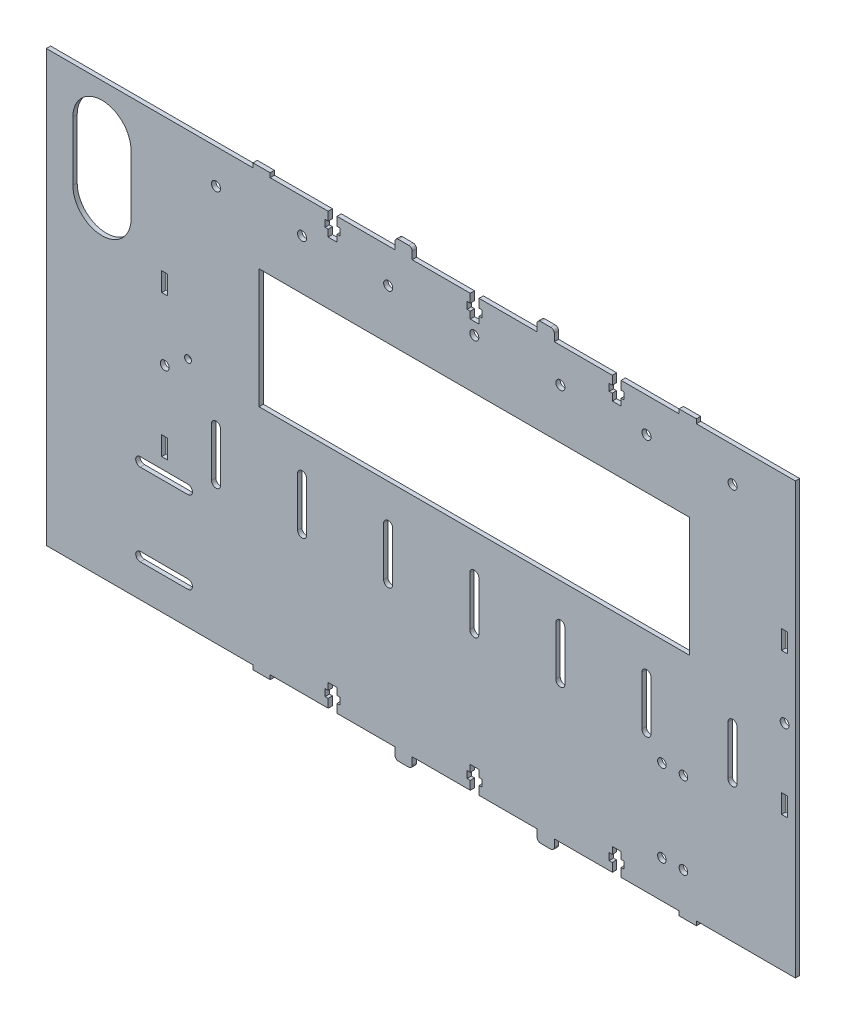
SolidWorks part; units mm, degrees
ref_plane "前视基准面" through (0, 0, 0) normal (0, 0, 1) x (1, 0, 0)
ref_plane "上视基准面" through (0, 0, 0) normal (0, 1, 0) x (1, 0, 0)
ref_plane "右视基准面" through (0, 0, 0) normal (1, 0, 0) x (0, 0, -1)
sketch "草图1" plane through (0, 0, 0) normal (0, 0, 1) x (1, 0, 0)
  line L0 (0, 0) -> (0, -4)
  line L1 (0, -4) -> (-1.45, -4)
  line L2 (-1.45, -4) -> (-1.45, -7.2)
  line L3 (-1.45, -7.2) -> (0, -7.2)
  line L4 (0, -7.2) -> (0, -10.4)
  line L5 (0, -10.4) -> (4.1, -10.4)
  line L6 (4.1, -10.4) -> (4.1, -7.2)
  line L7 (4.1, -7.2) -> (5.55, -7.2)
  line L8 (5.55, -7.2) -> (5.55, -4)
  line L9 (5.55, -4) -> (4.1, -4)
  line L10 (4.1, -4) -> (4.1, 0)
  line L11 (0, 0) -> (-26.95, 0)
  line L12 (-26.95, 0) -> (-26.95, 5)
  line L13 (-26.95, 5) -> (-34.95, 5)
  line L14 (-34.95, 5) -> (-34.95, 0)
  line L15 (2.05, -10.4) -> (2.05, -56.6) construction
  line L16 (-30.95, 5) -> (-30.95, 0) construction
  line L17 (-67.45, -4) -> (-66, -4)
  line L18 (-66, -7.2) -> (-67.45, -7.2)
  line L19 (-60.45, -7.2) -> (-61.9, -7.2)
  line L20 (-61.9, -4) -> (-60.45, -4)
  line L21 (-66, -4) -> (-66, 0)
  line L22 (-66, -10.4) -> (-66, -7.2)
  line L23 (-61.9, -10.4) -> (-66, -10.4)
  line L24 (-61.9, -7.2) -> (-61.9, -10.4)
  line L25 (-67.45, -7.2) -> (-67.45, -4)
  line L26 (-60.45, -4) -> (-60.45, -7.2)
  line L27 (-61.9, 0) -> (-61.9, -4)
  line L28 (-61.9, 0) -> (-34.95, 0)
  line L29 (31.05, 5) -> (39.05, 5)
  line L30 (31.05, 0) -> (31.05, 5)
  line L31 (39.05, 5) -> (39.05, 0)
  line L32 (4.1, 0) -> (31.05, 0)
  line L33 (66, 0) -> (39.05, 0)
  line L34 (66, 0) -> (66, -4)
  line L35 (64.55, -4) -> (64.55, -7.2)
  line L36 (71.55, -7.2) -> (71.55, -4)
  line L37 (66, -7.2) -> (66, -10.4)
  line L38 (66, -10.4) -> (70.1, -10.4)
  line L39 (70.1, -10.4) -> (70.1, -7.2)
  line L40 (70.1, -4) -> (70.1, 0)
  line L41 (66, -4) -> (64.55, -4)
  line L42 (64.55, -7.2) -> (66, -7.2)
  line L43 (70.1, -7.2) -> (71.55, -7.2)
  line L44 (71.55, -4) -> (70.1, -4)
  line L45 (68.05, -10.4) -> (68.05, -6.6) construction
  line L46 (70.1, 0) -> (97.05, 0)
  line L47 (132, 0) -> (105.05, 0)
  line L48 (97.05, 5) -> (97.05, 0)
  line L49 (105.05, 0) -> (105.05, 5)
  line L50 (105.05, 5) -> (97.05, 5)
  line L51 (-63.95, -10.4) -> (-63.95, -6.6) construction
  line L52 (-96.95, 5) -> (-96.95, 0) construction
  line L53 (-66, 0) -> (-92.95, 0)
  line L54 (-92.95, 5) -> (-92.95, 0)
  line L55 (-100.95, 5) -> (-92.95, 5)
  line L56 (-100.95, 0) -> (-100.95, 5)
  line L57 (-127.9, 0) -> (-100.95, 0)
  line L58 (2.05, -10.4) -> (-140.5, -10.4) construction
  line L59 (-127.9, 0) -> (-139.95, 0)
  line L60 (132, 0) -> (144.05, 0)
  line L64 (-139.95, 0) -> (-141.95, 0)
  line L66 (-96.95, -205) -> (-96.95, -200) construction
  line L79 (-63.95, -189.6) -> (-63.95, -193.4) construction
  line L101 (68.05, -189.6) -> (68.05, -193.4) construction
  line L102 (-30.95, -205) -> (-30.95, -200) construction
  line L103 (-127.9, -200) -> (-100.95, -200)
  line L104 (-100.95, -200) -> (-100.95, -205)
  line L137 (-141.95, 0) -> (-141.95, -200) construction
  line L138 (-141.95, -200) -> (-139.95, -200)
  line L140 (-143.35, -62.6) -> (-140.55, -62.6)
  line L141 (-143.35, -62.6) -> (-143.35, -71.4)
  line L142 (-143.35, -71.4) -> (-140.55, -71.4)
  line L143 (-140.55, -62.6) -> (-140.55, -71.4)
  line L144 (-143.35, -62.6) -> (-140.55, -71.4) construction
  line L145 (-143.35, -71.4) -> (-140.55, -62.6) construction
  line L146 (-141.95, -100) -> (-134.9383, -100) construction
  line L148 (-140.55, -137.4) -> (-140.55, -128.6)
  line L149 (-143.35, -137.4) -> (-143.35, -128.6)
  line L150 (-143.35, -128.6) -> (-140.55, -128.6)
  line L151 (-143.35, -137.4) -> (-140.55, -137.4)
  line L152 (-141.95, 0) -> (-146.95, 0)
  line L154 (-146.95, -200) -> (-141.95, -200)
  line L156 (146.05, -200) -> (144.05, -200)
  line L157 (151.05, -200) -> (146.05, -200)
  line L158 (144.05, 0) -> (146.05, 0)
  line L159 (146.05, 0) -> (151.05, 0)
  line L160 (151.05, 0) -> (151.05, -200)
  line L161 (146.05, -100) -> (139.0383, -100) construction
  line L162 (147.45, -71.4) -> (144.65, -62.6) construction
  line L163 (147.45, -62.6) -> (144.65, -71.4) construction
  line L164 (146.05, 0) -> (146.05, -200) construction
  line L165 (147.45, -137.4) -> (144.65, -137.4)
  line L166 (147.45, -128.6) -> (144.65, -128.6)
  line L167 (147.45, -137.4) -> (147.45, -128.6)
  line L168 (144.65, -137.4) -> (144.65, -128.6)
  line L169 (144.65, -62.6) -> (144.65, -71.4)
  line L170 (147.45, -71.4) -> (144.65, -71.4)
  line L171 (147.45, -62.6) -> (147.45, -71.4)
  line L172 (147.45, -62.6) -> (144.65, -62.6)
  line L173 (-100.95, -205) -> (-92.95, -205)
  line L174 (-92.95, -205) -> (-92.95, -200)
  line L175 (-66, -200) -> (-92.95, -200)
  line L176 (105.05, -205) -> (97.05, -205)
  line L177 (105.05, -200) -> (105.05, -205)
  line L178 (97.05, -205) -> (97.05, -200)
  line L179 (132, -200) -> (105.05, -200)
  line L180 (70.1, -200) -> (97.05, -200)
  line L181 (71.55, -196) -> (70.1, -196)
  line L182 (70.1, -192.8) -> (71.55, -192.8)
  line L183 (64.55, -192.8) -> (66, -192.8)
  line L184 (66, -196) -> (64.55, -196)
  line L185 (70.1, -196) -> (70.1, -200)
  line L186 (70.1, -189.6) -> (70.1, -192.8)
  line L187 (66, -189.6) -> (70.1, -189.6)
  line L188 (66, -192.8) -> (66, -189.6)
  line L189 (71.55, -192.8) -> (71.55, -196)
  line L190 (64.55, -196) -> (64.55, -192.8)
  line L191 (66, -200) -> (66, -196)
  line L192 (66, -200) -> (39.05, -200)
  line L193 (4.1, -200) -> (31.05, -200)
  line L194 (39.05, -205) -> (39.05, -200)
  line L195 (31.05, -200) -> (31.05, -205)
  line L196 (31.05, -205) -> (39.05, -205)
  line L197 (-61.9, -200) -> (-34.95, -200)
  line L198 (-61.9, -200) -> (-61.9, -196)
  line L199 (-60.45, -196) -> (-60.45, -192.8)
  line L200 (-67.45, -192.8) -> (-67.45, -196)
  line L201 (-61.9, -192.8) -> (-61.9, -189.6)
  line L202 (-61.9, -189.6) -> (-66, -189.6)
  line L203 (-66, -189.6) -> (-66, -192.8)
  line L204 (-66, -196) -> (-66, -200)
  line L205 (-61.9, -196) -> (-60.45, -196)
  line L206 (-60.45, -192.8) -> (-61.9, -192.8)
  line L207 (-66, -192.8) -> (-67.45, -192.8)
  line L208 (-67.45, -196) -> (-66, -196)
  line L209 (-34.95, -205) -> (-34.95, -200)
  line L210 (-26.95, -205) -> (-34.95, -205)
  line L211 (-26.95, -200) -> (-26.95, -205)
  line L212 (0, -200) -> (-26.95, -200)
  line L213 (4.1, -196) -> (4.1, -200)
  line L214 (5.55, -196) -> (4.1, -196)
  line L215 (5.55, -192.8) -> (5.55, -196)
  line L216 (4.1, -192.8) -> (5.55, -192.8)
  line L217 (4.1, -189.6) -> (4.1, -192.8)
  line L218 (0, -189.6) -> (4.1, -189.6)
  line L219 (0, -192.8) -> (0, -189.6)
  line L220 (-1.45, -192.8) -> (0, -192.8)
  line L221 (-1.45, -196) -> (-1.45, -192.8)
  line L222 (0, -196) -> (-1.45, -196)
  line L223 (0, -200) -> (0, -196)
  line L224 (-139.95, -200) -> (-127.9, -200)
  line L225 (132, -200) -> (144.05, -200)
  line L226 (-38.121, 0.7643) -> (-38.121, -54.2997) construction
  line L227 (-104.121, 0.7643) -> (-104.121, -54.2997) construction
  line L228 (137.879, -104.2357) -> (107.9873, -104.2357) construction
  line L229 (-104.121, -209.2357) -> (-104.121, -154.1717) construction
  line L230 (-38.121, -209.2357) -> (-38.121, -154.1717) construction
  line L231 (-78.121, -135.4214) -> (-78.121, -112.5786) construction
  line L232 (-80.221, -135.4214) -> (-80.221, -112.5786)
  line L233 (-76.021, -135.4214) -> (-76.021, -112.5786)
  line L234 (-38.121, -135.4214) -> (-38.121, -112.5786) construction
  line L235 (-98.121, -39.2357) -> (-98.121, -94.7357)
  line L236 (-98.121, -94.7357) -> (101.879, -94.7357)
  line L237 (-118.121, -135.4214) -> (-118.121, -112.5786) construction
  line L238 (-120.221, -135.4214) -> (-120.221, -112.5786)
  line L239 (-116.021, -135.4214) -> (-116.021, -112.5786)
  line L240 (-40.221, -135.4214) -> (-40.221, -112.5786)
  line L243 (-36.021, -135.4214) -> (-36.021, -112.5786)
  line L246 (1.879, -135.4214) -> (1.879, -112.5786) construction
  line L249 (-0.221, -135.4214) -> (-0.221, -112.5786)
  line L252 (3.979, -135.4214) -> (3.979, -112.5786)
  line L255 (101.879, -39.2357) -> (101.879, -94.7357)
  line L256 (-118.121, -16) -> (121.879, -16) construction
  line L257 (-118.121, -16) -> (-118.121, -111.5) construction
  line L258 (-118.121, -111.5) -> (121.879, -111.5) construction
  line L259 (-98.121, -39.2357) -> (101.879, -39.2357)
  line L260 (41.879, -135.4214) -> (41.879, -112.5786) construction
  line L261 (39.779, -135.4214) -> (39.779, -112.5786)
  line L262 (43.979, -135.4214) -> (43.979, -112.5786)
  line L263 (81.879, -135.4214) -> (81.879, -112.5786) construction
  line L264 (79.779, -135.4214) -> (79.779, -112.5786)
  line L265 (83.979, -135.4214) -> (83.979, -112.5786)
  line L266 (121.879, -135.4214) -> (121.879, -112.5786) construction
  line L267 (119.779, -135.4214) -> (119.779, -112.5786)
  line L268 (123.979, -135.4214) -> (123.979, -112.5786)
  line L269 (-171.1058, -21.4111) -> (-171.1058, -48.8744) construction
  line L270 (-146.95, 0) -> (-196.95, 0)
  line L271 (-146.95, 0) -> (-146.95, -200) construction
  line L272 (99.05, -182.5174) -> (99.05, -144.5174) construction
  line L273 (99.05, -144.5174) -> (89.05, -144.5174) construction
  line L274 (94.05, -144.5174) -> (94.05, -152.7968) construction
  line L275 (94.05, -152.7968) -> (-142.25, -152.7968) construction
  line L276 (-24.1, -152.7968) -> (-24.1, -162.5312) construction
  line L277 (-139.95, -200) -> (151.05, -200) construction
  line L278 (-153.3224, -144.5174) -> (-131.1776, -144.5174) construction
  line L279 (-153.3224, -142.4174) -> (-131.1776, -142.4174)
  line L280 (-153.3224, -146.6174) -> (-131.1776, -146.6174)
  line L281 (-153.3224, -182.627) -> (-131.1776, -182.627) construction
  line L282 (-153.3224, -180.527) -> (-131.1776, -180.527)
  line L283 (-153.3224, -184.727) -> (-131.1776, -184.727)
  line L284 (-146.95, -200) -> (-196.95, -200)
  line L285 (-196.95, 0) -> (-196.95, -200)
  line L286 (-157.5922, -21.4111) -> (-157.5922, -48.8744)
  line L287 (-184.6194, -21.4111) -> (-184.6194, -48.8744)
  circle A0 centre (-141.95, -100) radius 2.05
  circle A1 centre (146.05, -100) radius 2.05
  circle A3 centre (-118.121, -16) radius 2.1
  circle A4 centre (-78.121, -16) radius 2.1
  circle A5 centre (-38.121, -16) radius 2.1
  circle A6 centre (1.879, -16) radius 2.1
  circle A7 centre (41.879, -16) radius 2.1
  circle A8 centre (81.879, -16) radius 2.1
  arc A9 (-120.221, -135.4214) -> (-116.021, -135.4214) centre (-118.121, -135.4214) ccw
  arc A10 (-116.021, -112.5786) -> (-120.221, -112.5786) centre (-118.121, -112.5786) ccw
  circle A21 centre (99.05, -182.5174) radius 2
  circle A22 centre (99.05, -144.5174) radius 2
  circle A23 centre (89.05, -144.5174) radius 2
  circle A24 centre (89.0506, -182.627) radius 2
  circle A25 centre (-147.25, -182.5174) radius 2 construction
  circle A26 centre (-137.2506, -182.627) radius 2 construction
  circle A27 centre (-137.25, -144.5174) radius 2 construction
  circle A28 centre (-147.25, -144.5174) radius 2 construction
  arc A29 (-153.3224, -142.4174) -> (-153.3224, -146.6174) centre (-153.3224, -144.5174) ccw
  arc A30 (-131.1776, -146.6174) -> (-131.1776, -142.4174) centre (-131.1776, -144.5174) ccw
  arc A31 (-153.3224, -180.527) -> (-153.3224, -184.727) centre (-153.3224, -182.627) ccw
  arc A32 (-131.1776, -184.727) -> (-131.1776, -180.527) centre (-131.1776, -182.627) ccw
  arc A33 (-80.221, -135.4214) -> (-76.021, -135.4214) centre (-78.121, -135.4214) ccw
  arc A34 (-76.021, -112.5786) -> (-80.221, -112.5786) centre (-78.121, -112.5786) ccw
  arc A35 (-40.221, -135.4214) -> (-36.021, -135.4214) centre (-38.121, -135.4214) ccw
  arc A36 (-36.021, -112.5786) -> (-40.221, -112.5786) centre (-38.121, -112.5786) ccw
  arc A37 (-0.221, -135.4214) -> (3.979, -135.4214) centre (1.879, -135.4214) ccw
  arc A38 (3.979, -112.5786) -> (-0.221, -112.5786) centre (1.879, -112.5786) ccw
  arc A39 (39.779, -135.4214) -> (43.979, -135.4214) centre (41.879, -135.4214) ccw
  arc A40 (43.979, -112.5786) -> (39.779, -112.5786) centre (41.879, -112.5786) ccw
  arc A41 (79.779, -135.4214) -> (83.979, -135.4214) centre (81.879, -135.4214) ccw
  arc A42 (83.979, -112.5786) -> (79.779, -112.5786) centre (81.879, -112.5786) ccw
  circle A43 centre (121.879, -16) radius 2.1
  arc A44 (119.779, -135.4214) -> (123.979, -135.4214) centre (121.879, -135.4214) ccw
  arc A45 (123.979, -112.5786) -> (119.779, -112.5786) centre (121.879, -112.5786) ccw
  circle A46 centre (-131.1232, -92.0123) radius 1.5966
  arc A49 (-157.5922, -21.4111) -> (-184.6194, -21.4111) centre (-171.1058, -21.4111) ccw
  arc A50 (-184.6194, -48.8744) -> (-157.5922, -48.8744) centre (-171.1058, -48.8744) ccw
  point P139 (-141.95, -67)
  point P166 (146.05, -67)
  point P178 (-78.121, -124)
  point P200 (-118.121, -124)
  point P209 (-38.121, -124)
  point P216 (1.879, -124)
  point P223 (41.879, -124)
  point P230 (81.879, -124)
  point P237 (121.879, -124)
  point P249 (-171.1058, -35.1427)
  point P282 (-142.25, -144.5174)
  point P288 (-142.25, -182.627)
  dimension "D9" = 33
  dimension "D14" = 33
  dimension "D5" = 8
  dimension "D24" = 50
  dimension "D1" = 4.1
  dimension "D2" = 7
  dimension "D3" = 4
  dimension "D4" = 3.2
  dimension "D6" = 200
  dimension "D7" = 5
  dimension "D8" = 284
  dimension "D10" = 2.8
  dimension "D11" = 2
  dimension "D12" = 8.8
  dimension "D13" = 5
  dimension "D15" = 40
  dimension "D16" = 40
  dimension "D17" = 40
  dimension "D18" = 40
  dimension "D19" = 40
  dimension "D20" = 40
  dimension "D21" = 108
  dimension "D22" = 16
  dimension "D23" = 7
extrude "凸台-拉伸1" add sketch "草图1" along normal blind 2 contours L179 L225 L156 L157 L160 L159 L158 L60 L47 L49 L50 L48 L46 L40 L44 L36 L43 L39 L38 L37 L42 L35 L41 L34 L33 L31 L29 L30 L32 L10 L9 L8 L7 L6 L5 L4 L3 L2 L1 L0 L11 L12 L13 L14 L28 L27 L20 L26 L19 L24 L23 region at (-24.4618, -107.5951, 0)
sketch "草图2" plane through (0, 0, 0) normal (0, 1, 0) x (1, 0, 0)
  line L0 (-66, -1) -> (-61.9, -1)
  line L1 (-66, -2) -> (-66, 0) construction
  line L2 (-61.9, -2) -> (-61.9, 0) construction
  circle A0 centre (-63.95, -1) radius 2.05
sketch "草图3" plane through (0, -200, 0) normal (0, -1, 0) x (1, 0, 0)
  line L0 (-66, 1) -> (-61.9, 1)
  line L1 (-66, 2) -> (-66, 0) construction
  line L2 (-61.9, 2) -> (-61.9, 0) construction
  circle A0 centre (-63.95, 1) radius 2.05
sketch "草图4" plane through (0, 0, 2) normal (0, 0, 1) x (1, 0, 0)
  line L0 (-66, 0) -> (-92.95, 0) construction
  line L1 (90.1394, 11.0656) -> (110.8448, 11.0656)
  line L2 (90.1394, 11.0656) -> (90.1394, 2)
  line L3 (90.1394, 2) -> (110.8448, 2)
  line L4 (110.8448, 11.0656) -> (110.8448, 2)
  line L5 (129.0593, -220.504) -> (87.0868, -220.504)
  line L6 (129.0593, -220.504) -> (129.0593, -202)
  line L7 (129.0593, -202) -> (87.0868, -202)
  line L8 (87.0868, -220.504) -> (87.0868, -202)
  line L9 (-74.9592, -217.0386) -> (-125.8159, -217.0386)
  line L10 (-74.9592, -217.0386) -> (-74.9592, -202)
  line L11 (-74.9592, -202) -> (-125.8159, -202)
  line L12 (-125.8159, -217.0386) -> (-125.8159, -202)
  line L13 (-125.8159, 16.3207) -> (-86.3602, 16.3207)
  line L14 (-125.8159, 16.3207) -> (-125.8159, 2)
  line L15 (-125.8159, 2) -> (-86.3602, 2)
  line L16 (-86.3602, 16.3207) -> (-86.3602, 2)
  line L17 (132, 0) -> (105.05, 0) construction
  line L18 (132, -200) -> (105.05, -200) construction
  line L19 (-127.9, -200) -> (-100.95, -200) construction
  dimension "D1" = 2
  dimension "D2" = 2
  dimension "D3" = 2
  dimension "D4" = 2
extrude "切除-拉伸1" cut sketch "草图4" against normal blind 2
fillet "圆角1" radius 1.6 8 edges at (39.05, 5, 1) (31.05, 5, 1) (-26.95, 5, 1) (-34.95, 5, 1) (39.05, -205, 1) (31.05, -205, 1) (-26.95, -205, 1) (-34.95, -205, 1)
